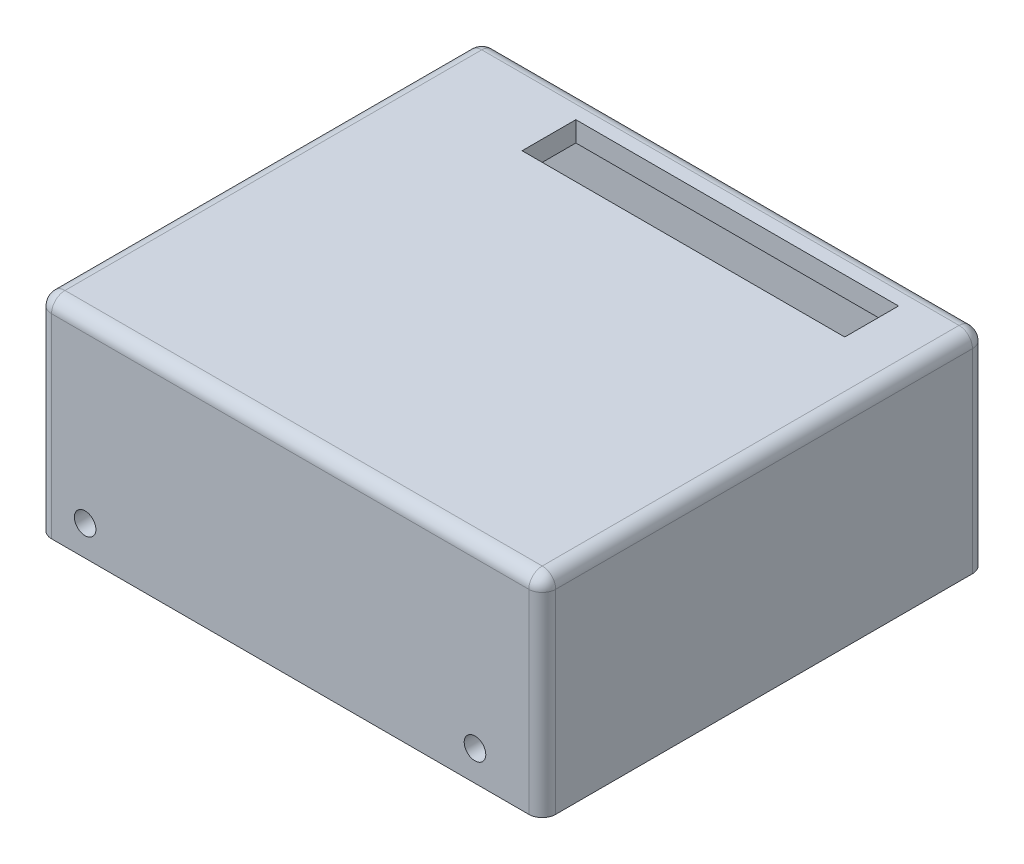
SolidWorks part; units mm, degrees
ref_plane "Front Plane" through (0, 0, 0) normal (0, 0, 1) x (1, 0, 0)
ref_plane "Top Plane" through (0, 0, 0) normal (0, 1, 0) x (1, 0, 0)
ref_plane "Right Plane" through (0, 0, 0) normal (1, 0, 0) x (0, 0, -1)
sketch "Sketch1" plane through (0, 0, 0) normal (0, -1, 0) x (1, 0, 0)
  line L0 (-3, 61) -> (-3, -5)
  line L1 (0, 58) -> (72, 58)
  line L2 (0, 58) -> (0, -2)
  line L3 (0, -2) -> (72, -2)
  line L4 (72, 58) -> (72, -2)
  line L5 (-3, -5) -> (75, -5)
  line L6 (75, 61) -> (75, -5)
  line L7 (-3, 61) -> (75, 61)
  dimension "D1" = 3
extrude "Boss-Extrude1" add sketch "Sketch1" against normal blind 28
sketch "Sketch2" plane through (0, 28, 0) normal (0, 1, 0) x (1, 0, 0)
  line L0 (0, 2) -> (72, 2) construction
  line L1 (66, 1) -> (18, 1)
  line L2 (66, 1) -> (66, -7)
  line L3 (66, -7) -> (18, -7)
  line L4 (18, 1) -> (18, -7)
  line L5 (72, 2) -> (72, -58) construction
  line L6 (75, -61) -> (-3, -61) construction
  line L7 (-3, 5) -> (75, 5)
  line L8 (-3, 5) -> (-3, -61)
  line L9 (-3, -61) -> (75, -61)
  line L10 (75, 5) -> (75, -61)
  dimension "D1" = 1
  dimension "D2" = 8
  dimension "D3" = 6
  dimension "D4" = 48
extrude "Boss-Extrude2" add sketch "Sketch2" along normal blind 3 contours L8 L7 L10 L9 | L2 L1 L4 L3
sketch "Sketch3" plane through (-3, 0, 0) normal (-1, 0, 0) x (0, 0, 1)
  line L0 (-5, 31) -> (-5, 0) construction
  line L1 (-5, 31) -> (61, 31)
  line L2 (-5, 31) -> (-5, 0)
  line L3 (-5, 0) -> (61, 0)
  line L4 (61, 31) -> (61, 0)
extrude "Cut-Extrude1" cut sketch "Sketch3" against normal blind 3
sketch "Sketch5" plane through (0, 0, 0) normal (-1, 0, 0) x (0, 0, 1)
  line L0 (-2, 28) -> (-2, 0) construction
  line L1 (58, 28) -> (-2, 28)
  line L2 (58, 28) -> (58, 24)
  line L3 (58, 24) -> (-2, 24)
  line L4 (-2, 28) -> (-2, 24)
  line L5 (58, 28) -> (58, 0) construction
  line L10 (-2, 28) -> (43, 28)
  line L11 (-2, 28) -> (-2, 16)
  line L12 (-2, 16) -> (43, 16)
  line L13 (43, 28) -> (43, 16)
  line M10 (58, 28) -> (58, 0)
  line M16 (-2, 0) -> (-2, 28)
  line M17 (-2, 28) -> (58, 28)
  dimension "D1" = 4
  dimension "D2" = 12
  dimension "D3" = 15
extrude "Boss-Extrude4" add sketch "Sketch5" against normal blind 3 contours L13 L3 M17 M16 | L1 L13 L3 M10 region at (0, 26, 50.5) region at (0, 26, 20.5)
extrude "Boss-Extrude5" add sketch "Sketch5<4>" against normal blind 3 contours L13 L3 L12 M16 region at (0, 20, 20.5)
sketch "Sketch5<4>" plane through (0, 0, 0) normal (-1, 0, 0) x (0, 0, 1) same geometry as "Sketch5"
fillet "Fillet1" radius 1 4 edges at (1.5, 16, -2) (1.5, 16, 43) (1.5, 24, 43) (1.5, 24, 58)
fillet "Fillet2" radius 2 8 edges at (0, 15.5, 61) (37.5, 31, 61) (75, 15.5, 61) (75, 31, 28) (0, 31, 28) (0, 15.5, -5) (37.5, 31, -5) (75, 15.5, -5)
sketch "Sketch6" plane through (0, 0, 58) normal (0, 0, -1) x (-1, 0, 0)
  circle A0 centre (-64.9946, 4.4986) radius 1.6056
  circle A1 centre (-7, 4.5) radius 1.6
extrude "Cut-Extrude2" cut sketch "Sketch6" against normal blind 17
extrude "Cut-Extrude4" cut sketch "Sketch6<3>" against normal blind 17 and the other way blind 103
sketch "Sketch6<3>" plane through (0, 0, 58) normal (0, 0, -1) x (-1, 0, 0) same geometry as "Sketch6"
